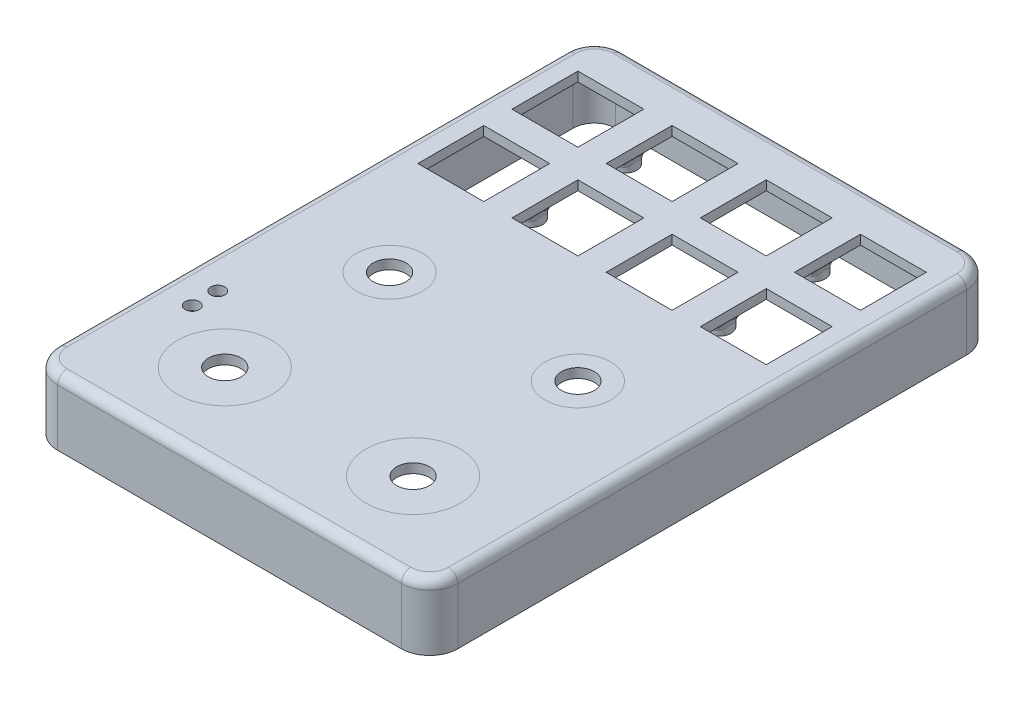
SolidWorks part; units mm, degrees
ref_plane "Plan de face" through (0, 0, 0) normal (0, 0, 1) x (1, 0, 0)
ref_plane "Plan de dessus" through (0, 0, 0) normal (0, 1, 0) x (1, 0, 0)
ref_plane "Plan de droite" through (0, 0, 0) normal (1, 0, 0) x (0, 0, -1)
sketch "Esquisse1" plane through (0, 0, 0) normal (0, 1, 0) x (1, 0, 0)
  line L1 (-42.5, -60) -> (42.5, -60)
  line L2 (-42.5, -60) -> (-42.5, 60)
  line L3 (-42.5, 60) -> (42.5, 60)
  line L4 (42.5, -60) -> (42.5, 60)
  line L5 (-42.5, -60) -> (42.5, 60) construction
  line L6 (-42.5, 60) -> (42.5, -60) construction
  point P0 (0, 0)
  dimension "D1" = 85
  dimension "D2" = 120
extrude "Boss.-Extru.1" add sketch "Esquisse1" along normal blind 2
sketch "Esquisse2" plane through (0, 2, 0) normal (0, 1, 0) x (1, 0, 0)
  line L0 (42.5, 60) -> (-42.5, 60) construction
  line L1 (-37, 51) -> (-23, 51)
  line L2 (-37, 51) -> (-37, 37)
  line L3 (-37, 37) -> (-23, 37)
  line L4 (-23, 51) -> (-23, 37)
  line L5 (-37, 51) -> (-23, 37) construction
  line L6 (-37, 37) -> (-23, 51) construction
  line L7 (-17, 51) -> (-3, 51)
  line L8 (-17, 51) -> (-17, 37)
  line L9 (-17, 37) -> (-3, 37)
  line L10 (-3, 51) -> (-3, 37)
  line L11 (-17, 51) -> (-3, 37) construction
  line L12 (-17, 37) -> (-3, 51) construction
  line L13 (3, 51) -> (17, 51)
  line L14 (3, 51) -> (3, 37)
  line L15 (3, 37) -> (17, 37)
  line L16 (17, 51) -> (17, 37)
  line L17 (3, 51) -> (17, 37) construction
  line L18 (3, 37) -> (17, 51) construction
  line L19 (23, 51) -> (37, 51)
  line L20 (23, 51) -> (23, 37)
  line L21 (23, 37) -> (37, 37)
  line L22 (37, 51) -> (37, 37)
  line L23 (23, 51) -> (37, 37) construction
  line L24 (23, 37) -> (37, 51) construction
  line L25 (23, 31) -> (37, 31)
  line L26 (23, 31) -> (23, 17)
  line L27 (23, 17) -> (37, 17)
  line L28 (37, 31) -> (37, 17)
  line L29 (23, 31) -> (37, 17) construction
  line L30 (23, 17) -> (37, 31) construction
  line L31 (17, 31) -> (3, 31)
  line L32 (17, 31) -> (17, 17)
  line L33 (17, 17) -> (3, 17)
  line L34 (3, 31) -> (3, 17)
  line L35 (17, 31) -> (3, 17) construction
  line L36 (17, 17) -> (3, 31) construction
  line L37 (-3, 31) -> (-17, 31)
  line L38 (-3, 31) -> (-3, 17)
  line L39 (-3, 17) -> (-17, 17)
  line L40 (-17, 31) -> (-17, 17)
  line L41 (-3, 31) -> (-17, 17) construction
  line L42 (-3, 17) -> (-17, 31) construction
  line L43 (-37, 31) -> (-23, 31)
  line L44 (-37, 31) -> (-37, 17)
  line L45 (-37, 17) -> (-23, 17)
  line L46 (-23, 31) -> (-23, 17)
  line L47 (-37, 31) -> (-23, 17) construction
  line L48 (-37, 17) -> (-23, 31) construction
  point P0 (-30, 44)
  point P5 (-10, 44)
  point P10 (10, 44)
  point P15 (30, 44)
  point P20 (30, 24)
  point P25 (10, 24)
  point P30 (-10, 24)
  point P35 (-30, 24)
  dimension "D1" = 14
  dimension "D2" = 14
  dimension "D3" = 20
  dimension "D4" = 20
  dimension "D5" = 20
  dimension "D6" = 10
  dimension "D7" = 16
  dimension "D8" = 20
extrude "Enlèv. mat.-Extru.1" cut sketch "Esquisse2" against normal blind 2
sketch "Esquisse3" plane through (0, 2, 0) normal (0, 1, 0) x (1, 0, 0)
  circle A0 centre (-20, -6) radius 7
  circle A1 centre (-20, -41) radius 10
  circle A2 centre (20, -6) radius 7
  circle A3 centre (20, -41) radius 10
  dimension "D1" = 14
  dimension "D6" = 20
  dimension "D2" = 35
  dimension "D3" = 20
  dimension "D4" = 20
  dimension "D5" = 6
extrude "Enlèv. mat.-Extru.2" cut sketch "Esquisse3" against normal blind 2
fillet "Congé1" radius 6 4 edges at (42.5, 1, 60) (-42.5, 1, 60) (-42.5, 1, -60) (42.5, 1, -60)
sketch "Esquisse5" plane through (0, 0, 0) normal (0, -1, 0) x (1, 0, 0)
  line L0 (-17, -31) -> (-17, -17) construction
  line L1 (-17, -51) -> (-17, -37) construction
  circle A0 centre (-20, -24) radius 2.5
  circle A1 centre (-20, -44) radius 2.5
  circle A3 centre (20, -44) radius 2.5
  circle A4 centre (20, -24) radius 2.5
  circle A7 centre (-20, -24) radius 0.95
  circle A9 centre (20, -24) radius 0.95
  circle A10 centre (20, -44) radius 0.95
  circle A12 centre (-20, -44) radius 0.95
  point P20 (-17, -24)
  point P23 (-17, -44)
  dimension "D1" = 5
  dimension "D4" = 1.9
  dimension "D2" = 20
  dimension "D3" = 20
extrude "Boss.-Extru.3" add sketch "Esquisse5" along normal blind 3
fillet "Congé2" radius 2 4 edges at (-20, 0, -46.5) (-20, 0, -26.5) (20, 0, -46.5) (20, 0, -26.5)
sketch "Esquisse6" plane through (0, 0, 0) normal (0, -1, 0) x (1, 0, 0)
  line L18 (-36.5, -58.5) -> (36.5, -58.5)
  line L19 (-42.5, -54) -> (-42.5, 54) construction
  line L20 (-36.5, 60) -> (36.5, 60) construction
  line L21 (41, -54) -> (41, 54)
  line L22 (36.5, 58.5) -> (-36.5, 58.5)
  line L23 (-41, 54) -> (-41, -54)
  line L24 (41, -54) -> (41, 54)
  line L25 (36.5, 58.5) -> (-36.5, 58.5)
  line L26 (-41, 54) -> (-41, -54)
  line L27 (42.5, 54) -> (42.5, -54) construction
  line L28 (36.5, -60) -> (-36.5, -60) construction
  line L29 (-42.5, -54) -> (-42.5, 54)
  line L30 (-36.5, 60) -> (36.5, 60)
  line L31 (42.5, 54) -> (42.5, -54)
  line L32 (36.5, -60) -> (-36.5, -60)
  arc A19 (-42.5, -54) -> (-36.5, -60) centre (-36.5, -54) ccw construction
  arc A20 (-36.5, 60) -> (-42.5, 54) centre (-36.5, 54) ccw construction
  arc A21 (42.5, 54) -> (36.5, 60) centre (36.5, 54) ccw construction
  arc A22 (36.5, -60) -> (42.5, -54) centre (36.5, -54) ccw construction
  arc A23 (-41, -54) -> (-36.5, -58.5) centre (-36.5, -54) ccw
  arc A24 (36.5, -58.5) -> (41, -54) centre (36.5, -54) ccw
  arc A25 (41, 54) -> (36.5, 58.5) centre (36.5, 54) ccw
  arc A26 (-36.5, 58.5) -> (-41, 54) centre (-36.5, 54) ccw
  arc A27 (-41, -54) -> (-36.5, -58.5) centre (-36.5, -54) ccw
  arc A28 (36.5, -58.5) -> (41, -54) centre (36.5, -54) ccw
  arc A29 (41, 54) -> (36.5, 58.5) centre (36.5, 54) ccw
  arc A30 (-36.5, 58.5) -> (-41, 54) centre (-36.5, 54) ccw
  arc A31 (-42.5, -54) -> (-36.5, -60) centre (-36.5, -54) ccw
  arc A32 (-36.5, 60) -> (-42.5, 54) centre (-36.5, 54) ccw
  arc A33 (42.5, 54) -> (36.5, 60) centre (36.5, 54) ccw
  arc A34 (36.5, -60) -> (42.5, -54) centre (36.5, -54) ccw
  dimension "D1" = 1.5
extrude "Boss.-Extru.4" add sketch "Esquisse6" along normal blind 12
sketch "Esquisse7" plane through (0, 0, 0) normal (0, -1, 0) x (1, 0, 0)
  line L0 (-42.5, 54) -> (-42.5, -54) construction
  line L1 (36.5, 60) -> (-36.5, 60) construction
  line L2 (42.5, -54) -> (42.5, 54) construction
  circle A0 centre (-35.93, 49.1) radius 4
  circle A1 centre (35.93, 49.1) radius 4
  circle A2 centre (-35.93, 49.1) radius 2.15
  circle A3 centre (35.93, 49.1) radius 2.15
  dimension "D1" = 6.57
  dimension "D4" = 8
  dimension "D5" = 4.3
  dimension "D2" = 10.9
  dimension "D3" = 6.57
extrude "Boss.-Extru.5" add sketch "Esquisse7" along normal blind 6
fillet "Congé5" radius 2 8 edges at (39.682, 0, 57.182) (41, 0, 0) (39.682, 0, -57.182) (0, 0, -58.5) (-39.682, 0, -57.182) (-41, 0, 0) (-39.682, 0, 57.182) (0, 0, 58.5)
sketch "Esquisse9" plane through (0, 2, 0) normal (0, 1, 0) x (1, 0, 0)
  circle A0 centre (-20, -41) radius 10 construction
  circle A1 centre (20, -41) radius 10 construction
  circle A2 centre (20, -6) radius 7 construction
  circle A3 centre (-20, -6) radius 7 construction
  circle A4 centre (-20, -41) radius 10
  circle A5 centre (20, -41) radius 10
  circle A6 centre (20, -6) radius 7
  circle A7 centre (-20, -6) radius 7
  circle A8 centre (-20, -6) radius 3.475
  circle A9 centre (-20, -41) radius 3.475
  circle A10 centre (20, -41) radius 3.475
  circle A11 centre (20, -6) radius 3.475
  dimension "D1" = 6.95
extrude "Boss.-Extru.6" add sketch "Esquisse9" against normal blind 2 separate body
fillet "Congé6" radius 2 8 edges at (40.7426, 2, 58.2426) (0, 2, 60) (-40.7426, 2, 58.2426) (-42.5, 2, 0) (-40.7426, 2, -58.2426) (0, 2, -60) (40.7426, 2, -58.2426) (42.5, 2, 0)
sketch "Esquisse10" plane through (0, 0, -60) normal (0, 0, -1) x (-1, 0, 0)
  line L0 (-3, -1.4) -> (3, -1.4) construction
  line L1 (-3, 0.35) -> (3, 0.35)
  line L2 (-3, -3.15) -> (3, -3.15)
  arc A0 (-3, 0.35) -> (-3, -3.15) centre (-3, -1.4) ccw
  arc A1 (3, -3.15) -> (3, 0.35) centre (3, -1.4) ccw
  point P2 (0, -1.4)
  point P7 (0, 0)
  dimension "D1" = 1.4
  dimension "D2" = 3.5
  dimension "D3" = 6
extrude "Enlèv. mat.-Extru.3" cut sketch "Esquisse10" against normal blind 8.5
sketch "Esquisse11" plane through (0, 2, 0) normal (0, 1, 0) x (1, 0, 0)
  line L0 (-42.5, -54) -> (-42.5, 54) construction
  circle A0 centre (-34.82, -27.68) radius 1.5
  circle A1 centre (-34.82, -33.08) radius 1.5
  point P7 (0, 0)
  dimension "D1" = 3
  dimension "D2" = 5.4
  dimension "D3" = 7.68
  dimension "D4" = 27.68
extrude "Enlèv. mat.-Extru.4" cut sketch "Esquisse11" against normal blind 3
